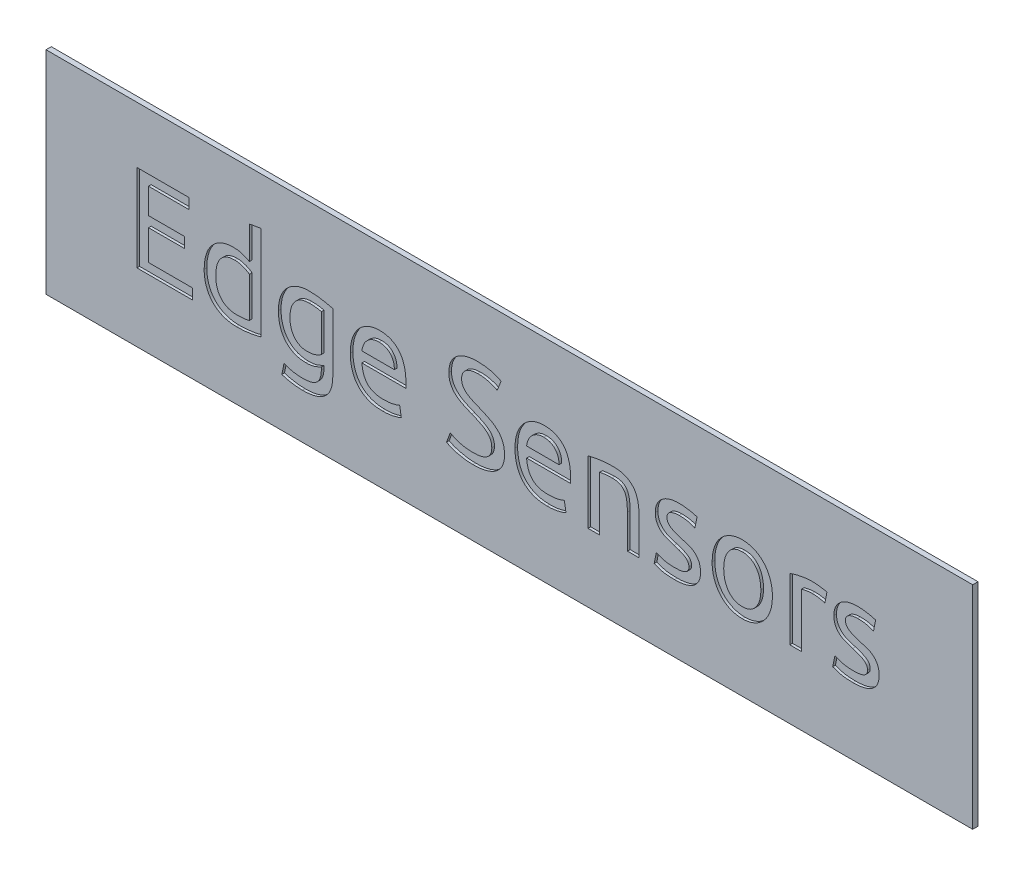
SolidWorks part; units mm, degrees
ref_plane "Front Plane" through (0, 0, 0) normal (0, 0, 1) x (1, 0, 0)
ref_plane "Top Plane" through (0, 0, 0) normal (0, 1, 0) x (1, 0, 0)
ref_plane "Right Plane" through (0, 0, 0) normal (1, 0, 0) x (0, 0, -1)
sketch "Sketch1" plane through (0, 0, 0) normal (0, 0, 1) x (1, 0, 0)
  line L1 (17.5, -4) -> (-17.5, -4)
  line L2 (17.5, -4) -> (17.5, 4)
  line L3 (17.5, 4) -> (-17.5, 4)
  line L4 (-17.5, -4) -> (-17.5, 4)
  line L5 (17.5, -4) -> (-17.5, 4) construction
  line L6 (17.5, 4) -> (-17.5, -4) construction
  point P0 (0, 0)
  dimension "D1" = 8
  dimension "D2" = 35
extrude "Boss-Extrude1" add sketch "Sketch1" along normal mid plane 0.2
sketch "Sketch2" plane through (0, 0, 0.1) normal (0, 0, 1) x (1, 0, 0)
  text T0 "LASER" font "Ubuntu" height in points 12
extrude "Cut-Extrude1" [suppressed] cut sketch "Sketch2" against normal blind 0.1
sketch "Sketch3" plane through (0, 0, 0.1) normal (0, 0, 1) x (1, 0, 0)
  text T0 "MOTOR  X" font "Ubuntu" height in points 12
extrude "Cut-Extrude2" [suppressed] cut sketch "Sketch3" against normal blind 0.1
sketch "Sketch4" [suppressed] plane through (0, 0, 0.1) normal (0, 0, 1) x (1, 0, 0)
  text T0 "MOTOR  Y" font "Ubuntu" height in points 12
extrude "Cut-Extrude3" [suppressed] cut sketch "Sketch4" against normal blind 0.1
sketch "Sketch5" plane through (0, 0, 0.1) normal (0, 0, 1) x (1, 0, 0)
  text T0 "Edge Sensors" font "Ubuntu" height in points 12
extrude "Cut-Extrude4" cut sketch "Sketch5" against normal blind 0.1
sketch "Sketch6" [suppressed] plane through (0, 0, 0.1) normal (0, 0, 1) x (1, 0, 0)
  text T0 "ON  LASER  OFF" font "Ubuntu" height in points 12
extrude "Cut-Extrude5" [suppressed] cut sketch "Sketch6" against normal blind 0.1
sketch "Sketch7" [suppressed] plane through (0, 0, 0.1) normal (0, 0, 1) x (1, 0, 0)
  text T0 "ON  PWR  OFF" font "Ubuntu" height in points 12
extrude "Cut-Extrude6" [suppressed] cut sketch "Sketch7" against normal blind 0.1
sketch "Sketch9" [suppressed] plane through (0, 0, 0.1) normal (0, 0, 1) x (1, 0, 0)
  text T0 "MOTOR  Z" font "Ubuntu" height in points 12
extrude "Cut-Extrude7" [suppressed] cut sketch "Sketch9" against normal blind 0.1
sketch "Sketch10" [suppressed] plane through (0, 0, 0.1) normal (0, 0, 1) x (1, 0, 0)
  text T0 "USB Device" font "Ubuntu" height in points 12
extrude "Cut-Extrude8" [suppressed] cut sketch "Sketch10" against normal blind 0.1
